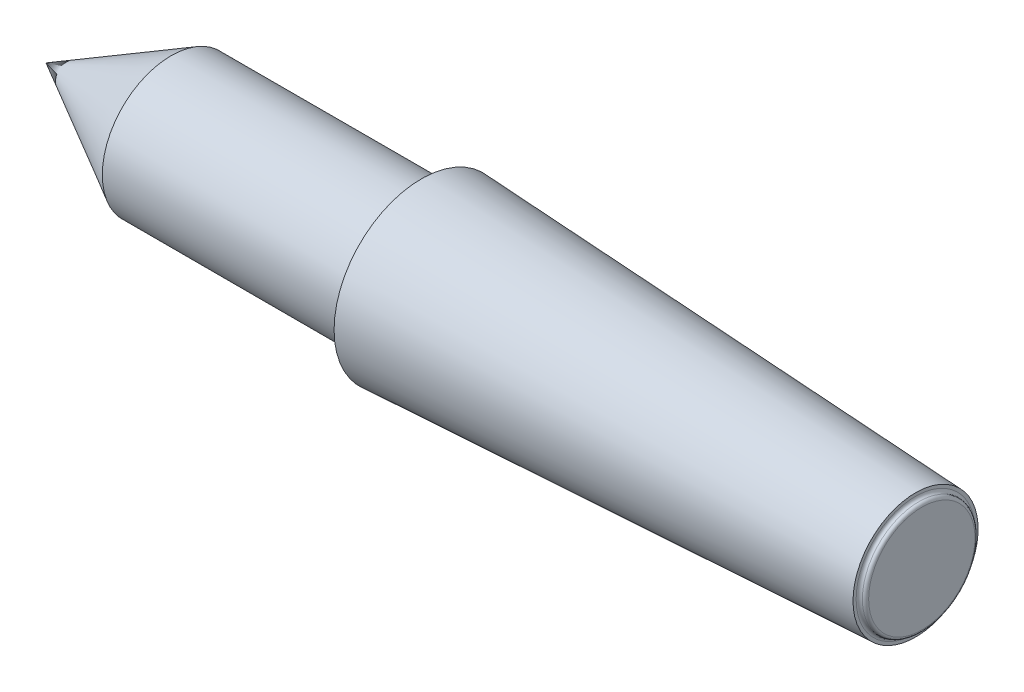
SolidWorks part; units mm, degrees
ref_plane "前视基准面" through (0, 0, 0) normal (0, 0, 1) x (1, 0, 0)
ref_plane "上视基准面" through (0, 0, 0) normal (0, 1, 0) x (1, 0, 0)
ref_plane "右视基准面" through (0, 0, 0) normal (1, 0, 0) x (0, 0, -1)
sketch "草图1" plane through (0, 0, 0) normal (0, 1, 0) x (1, 0, 0)
  line L0 (-857.4508, 0) -> (42015.0885, 0) construction
  line L1 (-140, 0) -> (-120, 11)
  line L2 (-120, 11) -> (-80, 11)
  line L3 (-80, 11) -> (-80, 13.95)
  line L4 (-80, 13.95) -> (-1, 10)
  line L5 (-1, 10) -> (-1, 9)
  line L6 (-1, 9) -> (0, 9)
  line L7 (0, 9) -> (0, 0)
  line L8 (0, 0) -> (-140, 0)
  line L9 (-80, 12.95) -> (-60, 12.95) construction
  dimension "D1" = 20
  dimension "D2" = 11
  dimension "D3" = 10
  dimension "D4" = 9
  dimension "D5" = 79
  dimension "D6" = 40
  dimension "D7" = 140
  dimension "D8" = 20
  dimension "D9" = 1
revolve "旋转1" add sketch "草图1" angle 360 about L0
fillet "圆角1" radius 0.5 3 edges at (0, 0, 9) (-1, 0, 9) (-80, 0, 11)
